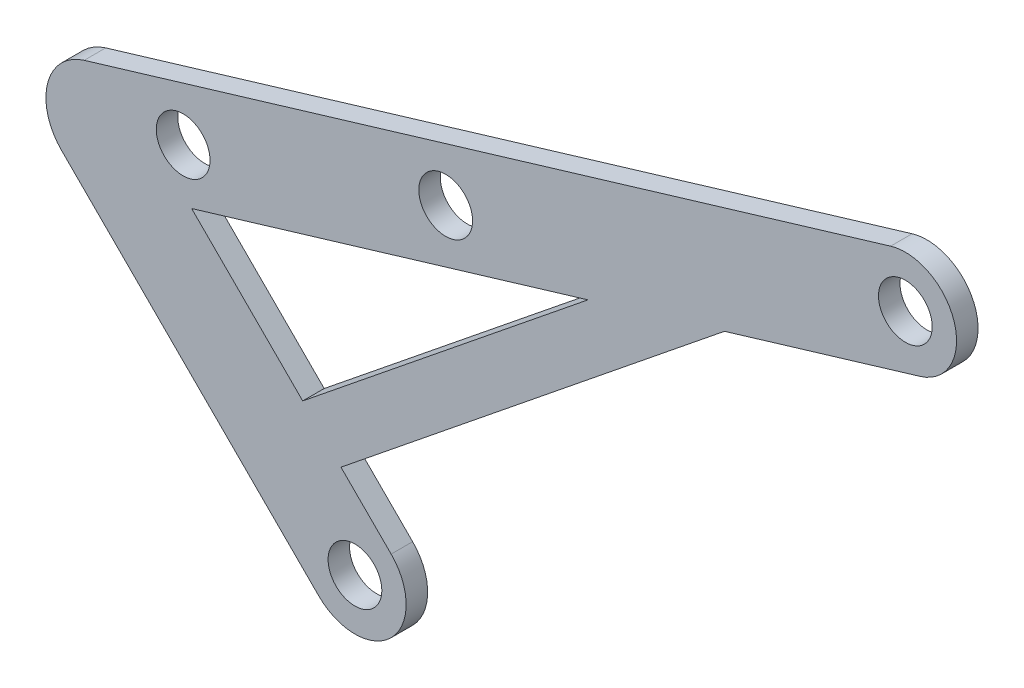
SolidWorks part; units mm, degrees
ref_plane "Front Plane" through (0, 0, 0) normal (0, 0, 1) x (1, 0, 0)
ref_plane "Top Plane" through (0, 0, 0) normal (0, 1, 0) x (1, 0, 0)
ref_plane "Right Plane" through (0, 0, 0) normal (1, 0, 0) x (0, 0, -1)
sketch "Sketch2" plane through (0, 0, 0) normal (0, 0, 1) x (1, 0, 0)
  line L0 (-41.3444, 0) -> (-91.4355, 0) construction
  line L1 (-91.4355, 0) -> (-77.9651, 13.4704) construction
  line L2 (-91.4355, 0) -> (-151.0973, 59.6619) construction
  line L3 (-77.9651, 13.4704) -> (-115.0845, 50.5899) construction
  line L4 (-100.3554, 74.9059) -> (23.9386, 112.2467) construction
  line L5 (-115.0845, 50.5899) -> (13.5223, 89.2263) construction
  line L6 (-100.3554, 74.9059) -> (-167.6048, 54.7027) construction
  line L7 (-77.9651, 13.4704) -> (-115.0845, 50.5899)
  line L8 (13.5223, 89.2263) -> (20.4402, 91.3046) construction
  line L9 (-115.0845, 50.5899) -> (20.4402, 91.3046)
  line L12 (-94.4179, 29.9232) -> (-41.3444, 72.7431)
  line L13 (-87.3002, 22.8055) -> (-15.9478, 80.3728)
  line L14 (-41.3444, 72.7431) -> (-15.9478, 80.3728)
  line L15 (-94.4179, 29.9232) -> (-87.3002, 22.8055)
  line L16 (-41.3444, 72.7431) -> (-35.0238, 64.909) construction
  line L17 (-41.3444, 72.7431) -> (-47.051, 68.139) construction
  line L18 (-94.8743, 56.6615) -> (-100.3554, 74.9059) construction
  line L19 (20.4402, 91.3046) -> (14.9591, 109.5491) construction
  line L20 (14.9591, 109.5491) -> (-151.0973, 59.6619)
  line L21 (-151.0973, 59.6619) -> (-91.4355, 0)
  arc A0 (-77.9651, 13.4704) -> (-91.4355, 0) centre (-84.7003, 6.7352) cw
  circle A3 centre (-84.7003, 6.7352) radius 5
  arc A4 (14.9591, 109.5491) -> (20.4402, 91.3046) centre (17.6996, 100.4268) cw
  circle A5 centre (17.6996, 100.4268) radius 5
  dimension "D12" = 10
  dimension "D2" = 10
  dimension "D1" = 45
  dimension "D4" = 52.4949
  dimension "D6" = 19.05
  dimension "D8" = 61.721
  dimension "D9" = 134.2851
  dimension "D10" = 90
  dimension "D13" = 90
  dimension "D14" = 68.1934
  dimension "D15" = 10.066
  dimension "D16" = 10.066
extrude "Boss-Extrude3" add sketch "Sketch2" along normal blind 4 contours A4 L20 L21 A0 L7 L9 A5 A3 | L7 L13 L9 L12 region at (-79.4569, 1.4918, 0) region at (-59.3545, 51.4674, 0)
fillet "Fillet3" radius 10 1 edges at (-151.0973, 59.6619, 2)
sketch "Sketch5" plane through (0, 0, 4) normal (0, 0, 1) x (1, 0, 0)
  line L0 (-119.4039, 69.1833) -> (-113.9228, 50.9389) construction
  line L1 (14.9591, 109.5491) -> (-135.0702, 64.4768) construction
  line L2 (-115.0845, 50.5899) -> (-41.3444, 72.7431) construction
  line L3 (-116.6633, 60.0611) -> (-67.8199, 74.7348) construction
  circle A0 centre (-116.6633, 60.0611) radius 5
  circle A1 centre (-67.8199, 74.7348) radius 5
  dimension "D2" = 10
  dimension "D5" = 10
  dimension "D1" = 90
  dimension "D3" = 90
  dimension "D4" = 51
extrude "Cut-Extrude3" cut sketch "Sketch5" against normal blind 4
